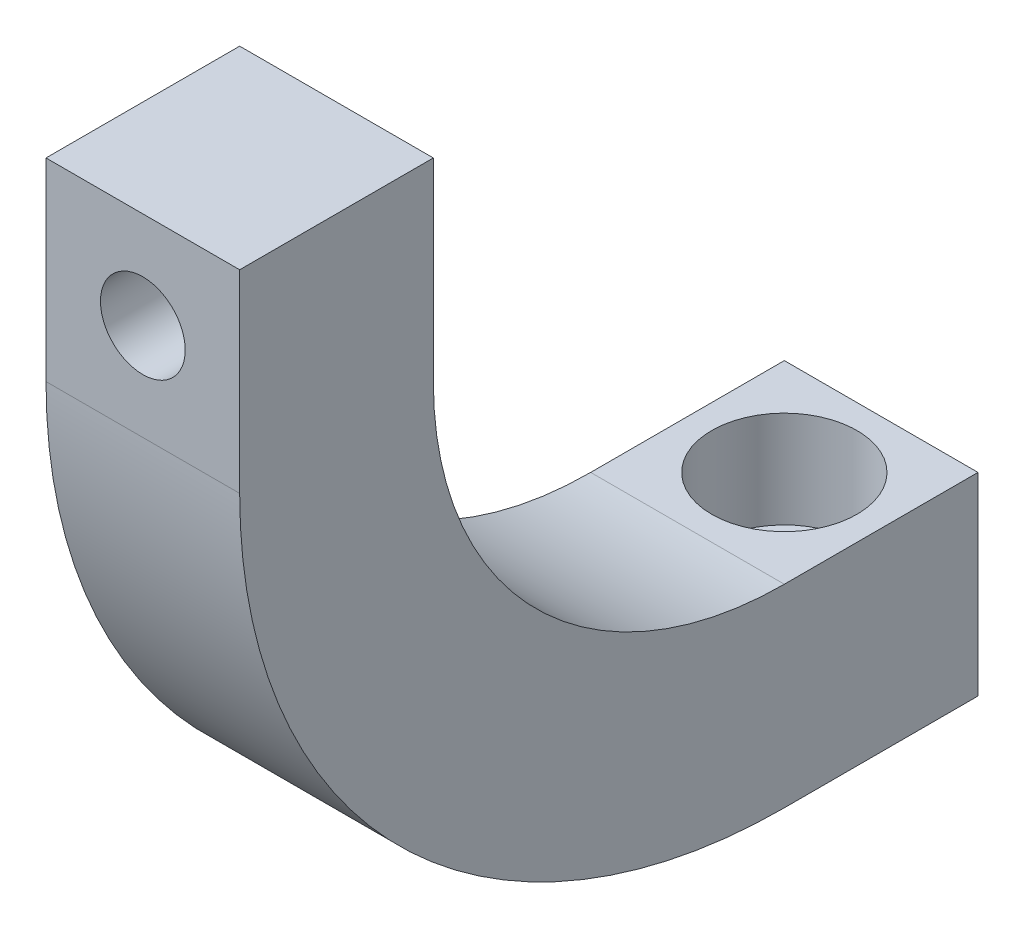
SolidWorks part; units mm, degrees
ref_plane "Front Plane" through (0, 0, 0) normal (0, 0, 1) x (1, 0, 0)
ref_plane "Top Plane" through (0, 0, 0) normal (0, 1, 0) x (1, 0, 0)
ref_plane "Right Plane" through (0, 0, 0) normal (1, 0, 0) x (0, 0, -1)
ref_axis "Z" through (0, 0, 22.75) along (0, 0, -1)
sketch "Sketch4" plane through (0, 0, 0) normal (0, 0, 1) x (1, 0, 0)
  circle A0 centre (0, 0) radius 17.5 construction
  dimension "D1" = 35
sketch "Sketch5" plane through (0, 0, 0) normal (1, 0, 0) x (0, 0, -1)
  line L0 (-18.5, 4) -> (-18.5, 0)
  line L1 (-18.5, 0) -> (-18.5, -4)
  line L2 (-26.5, -4) -> (-26.5, 4)
  line L6 (-26.5, 4) -> (-18.5, 4)
  line L12 (-22.75, 0) -> (-13.0351, 0) construction
  line L13 (0, 0) -> (-14.9091, -14.9091) construction
  line L14 (0, 0) -> (7.0065, 0) construction
  line L15 (0, -18.5) -> (-4, -18.5)
  line L16 (4, -18.5) -> (0, -18.5)
  line L17 (-4, -26.5) -> (4, -26.5)
  line L18 (4, -26.5) -> (4, -18.5)
  circle A0 centre (0, 0) radius 14 construction
  arc A1 (-18.5, -4) -> (-4, -18.5) centre (-4, -4) ccw
  arc A2 (-26.5, -4) -> (-4, -26.5) centre (-4, -4) ccw
  point P2 (9.4307, -21)
  point P4 (0, -2.1363)
  dimension "D1" = 28
  dimension "D4" = 4
  dimension "D2" = 45
  dimension "D3" = 8
  dimension "D5" = 18.5
sketch "Sketch6" plane through (0, 0, 0) normal (0, 1, 0) x (1, 0, 0)
  circle A0 centre (0, 0) radius 17.5 construction
  dimension "D1" = 35
extrude "Boss-Extrude1" add sketch "Sketch5" along normal blind 4 and the other way blind 4
sketch "Sketch7" plane through (0, 0, 0) normal (0, 0, 1) x (1, 0, 0)
  circle A0 centre (0, 0) radius 1.75
  dimension "D1" = 3.5
extrude "Cut-Extrude1" cut sketch "Sketch7" along normal through all
sketch "Sketch8" plane through (0, 0, 0) normal (0, 1, 0) x (1, 0, 0)
  circle A0 centre (0, 0) radius 1.75
  dimension "D1" = 3.5
extrude "Cut-Extrude2" cut sketch "Sketch8" against normal through all
ref_axis "Y" through (0, -9.3489, 0) along (0, -1, 0)
sketch "Sketch9" plane through (0, -18.5, 0) normal (0, 1, 0) x (1, 0, 0)
  circle A0 centre (0, 0) radius 3
  dimension "D1" = 6
extrude "Cut-Extrude4" cut sketch "Sketch9" against normal blind 4
sketch "Sketch10" plane through (0, 0, 18.5) normal (0, 0, -1) x (-1, 0, 0)
  circle A0 centre (0, 0) radius 3
  dimension "D1" = 6
extrude "Cut-Extrude5" cut sketch "Sketch10" against normal blind 4
equation "\"rbracket-width\"= \"L2Thickness\""
equation "\"EyeCaptureRadius\"= ( \"EyeDiameter\" + \"EyeClearance\" ) / 2"
equation "\"rbracket_planetocenterline_dist\"= \"BasePlaneDistance\""
equation "\"EyeDiameter\" = 35"
equation "\"BasePlaneDistance\" = \"EyeDiameter\"/2+19.84"
equation "\"EyeClearance\" = 2"
equation "\"D1@Sketch4\"=\"EyeDiameter\""
equation "\"D1@Sketch6\"=\"EyeDiameter\""
equation "\"D1@Boss-Extrude1\"=\"rbracket-width\"/2"
equation "\"D2@Boss-Extrude1\"=\"rbracket-width\"/2"
equation "\"L2Thickness\" = 8"
equation "\"D3@Sketch5\"=\"L2Thickness\""
equation "\"D5@Sketch5\"=(\"EyeDiameter\"+\"EyeClearance\")/2"
